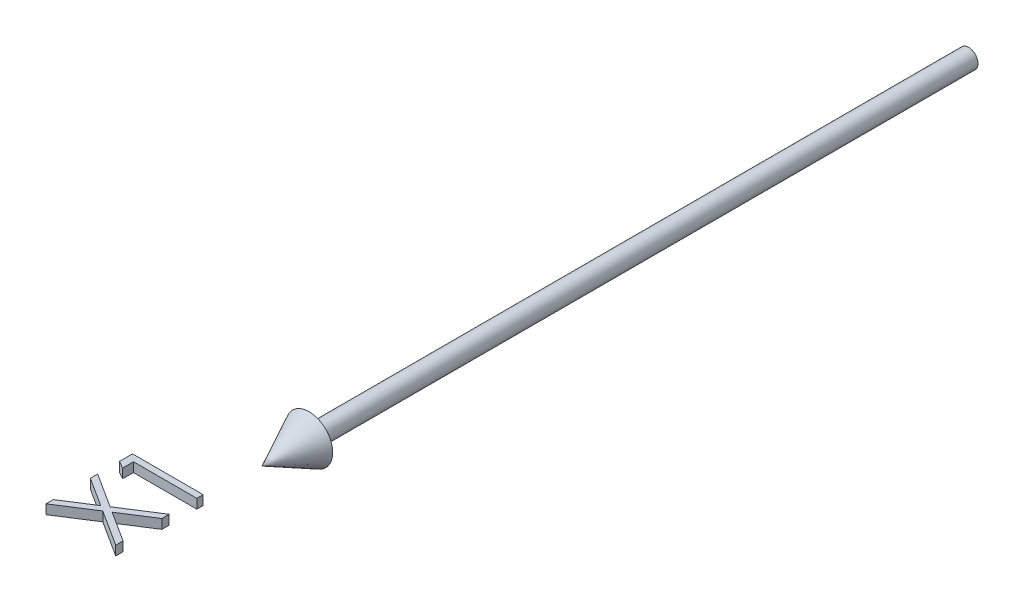
SolidWorks part; units mm, degrees
ref_plane "Front Plane" through (0, 0, 0) normal (0, 0, 1) x (1, 0, 0)
ref_plane "Top Plane" through (0, 0, 0) normal (0, 1, 0) x (1, 0, 0)
ref_plane "Right Plane" through (0, 0, 0) normal (1, 0, 0) x (0, 0, -1)
sketch "Sketch2" plane through (0, 0, 0) normal (0, 1, 0) x (1, 0, 0)
  line L0 (0, 41.95) -> (0, -114.4521) construction
  line L1 (-36.8894, 0) -> (41.4965, 0) construction
  line L2 (0, -150) -> (5, -140)
  line L3 (5, -140) -> (2, -140)
  line L4 (2, -140) -> (2, 0)
  line L5 (2, 0) -> (0, 0)
  line L6 (0, 0) -> (0, -150)
  dimension "D1" = 150
  dimension "D2" = 2
  dimension "D3" = 10
  dimension "D4" = 5
revolve "Revolve1" add sketch "Sketch2" angle 360 about L0
sketch "Sketch3" plane through (0, 0, 0) normal (0, 1, 0) x (1, 0, 0)
  line L0 (0, -157.5) -> (0, -264.5938) construction
  line L1 (-18.6107, 0) -> (18.3141, 0) construction
  text T0 "X1" font "Century Gothic" height 15
  point P3 (0, -264.5938)
  point P4 (0, -157.9774)
  dimension "D1" = 157.5
extrude "Boss-Extrude1" add sketch "Sketch3" against normal blind 1 and the other way blind 1 separate body
equation "\"D1@Sketch2\"=\"frame_arrow_length\""
equation "\"D2@Sketch2\"=\"frame_arrow_odA\"/2"
equation "\"D4@Sketch2\"=\"frame_arrow_head_od\""
equation "\"D3@Sketch2\"=\"frame_arrow_head_length\""
equation "\"frame_arrow_length\"=150"
equation "\"frame_arrow_head_length\"=10"
equation "\"frame_arrow_head_od\"=5"
equation "\"frame_arrow_odA\"=4"
equation "\"D1@Sketch3\"=\"frame_arrow_length\"*1.05"
